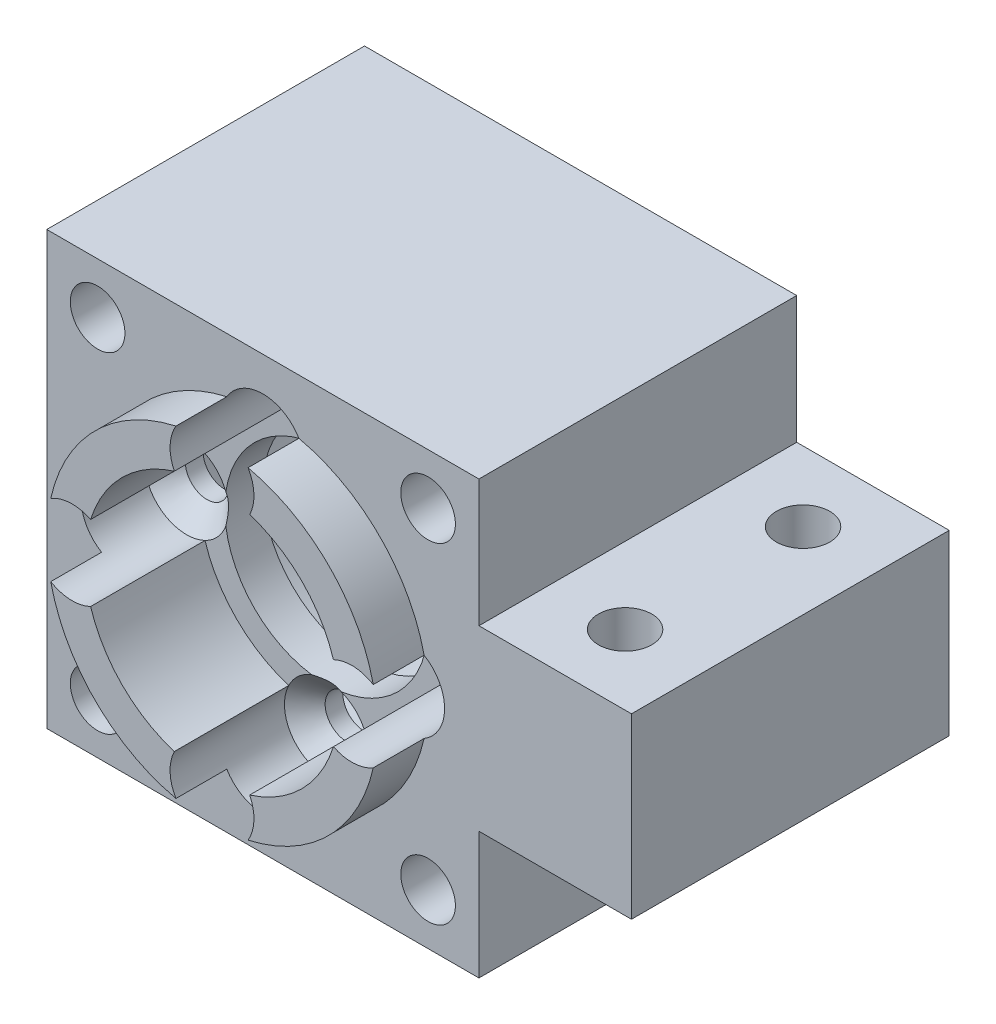
SolidWorks part; units mm, degrees
material "1060 合金"
ref_plane "前视基准面" through (0, 0, 0) normal (0, 0, 1) x (1, 0, 0)
ref_plane "上视基准面" through (0, 0, 0) normal (0, 1, 0) x (1, 0, 0)
ref_plane "右视基准面" through (0, 0, 0) normal (1, 0, 0) x (0, 0, -1)
sketch "草图1" plane through (0, 0, 0) normal (1, 0, 0) x (0, 0, -1)
  line L0 (0, 0) -> (85.2801, 0) construction
  line L1 (0, 0) -> (0, 40.8583) construction
  line L2 (0, 13) -> (0, 10)
  line L3 (0, 10) -> (9, 10)
  line L4 (9, 10) -> (9, 8)
  line L5 (9, 8) -> (12, 8)
  line L6 (12, 8) -> (12, 14)
  line L7 (12, 14) -> (29, 14)
  line L8 (29, 14) -> (29, 16)
  line L9 (29, 16) -> (4, 16)
  line L10 (0, 13) -> (4, 13)
  line L11 (4, 13) -> (4, 16)
  dimension "D1" = 8
  dimension "D2" = 3
  dimension "D3" = 13
  dimension "D4" = 14
  dimension "D5" = 2
  dimension "D6" = 17
  dimension "D7" = 4
  dimension "D8" = 8
  dimension "D9" = 10
revolve "旋转1" add sketch "草图1" angle 360 about L0
hole_wizard "打孔尺寸(%根据十字)槽沉头木螺钉的类型1" positions "草图3" profile "草图2" countersink size "M3" standard "GB" end condition through all
sketch "草图3" plane through (0, 0, 0) normal (0, 0, 1) x (1, 0, 0)
  line L0 (11, 0) -> (0, 0) construction
  line L2 (0, 0) -> (4.7674, 0) construction
  line L3 (0, 0) -> (0, 6.1766) construction
  circle A0 centre (0, 0) radius 11 construction
  point P0 (11, 0)
  point P12 (0, -11)
  point P13 (-11, 0)
  point P14 (0, 11)
  dimension "D1" = 22
  dimension "D2" = 4
sketch "草图2" plane through (11, 0, 0) normal (1, 0, 0) x (0, -1, 0)
  line L0 (0, 0) -> (0, 29)
  line L1 (0, 29) -> (1.7, 29)
  line L2 (1.7, 29) -> (1.7, 10.6)
  line L3 (1.7, 10.6) -> (3.3, 9)
  line L4 (3.3, 9) -> (3.3, 0)
  line L6 (3.3, 0) -> (0, 0)
  line L7 (-1.7, 10.6) -> (-3.3, 9) construction
  line L11 (0, -6.35) -> (0, 107.95) construction
  dimension "通孔孔直径" = 3.4
  dimension "通孔孔深度" = 29
  dimension "锥形沉头孔直径" = 6.6
  dimension "锥形沉头孔角度" = 90
  dimension "头间隙" = 9
sketch "草图4" plane through (0, 0, -4) normal (0, 0, 1) x (1, 0, 0)
  line L1 (-17, -17) -> (17, -17)
  line L2 (-17, -17) -> (-17, 17)
  line L3 (-17, 17) -> (17, 17)
  line L4 (17, -17) -> (17, 17)
  line L5 (-17, -17) -> (17, 17) construction
  line L6 (-17, 17) -> (17, -17) construction
  circle A0 centre (0, 0) radius 16
  circle A1 centre (0, 0) radius 16 construction
  point P0 (0, 0)
  dimension "D1" = 34
extrude "凸台-拉伸1" add sketch "草图4" against normal up to surface (25 mm away) up to face at (16, 0, -29)
sketch "草图11" [suppressed] plane through (0, 0, -29) normal (0, 0, -1) x (-1, 0, 0)
  line L0 (0, 0) -> (0, 25.5096) construction
  line L3 (-17, 17) -> (17, 17) construction
  line L4 (-10, 9.798) -> (10, 9.798) construction
  line L5 (-10, 9.798) -> (-10, 17)
  line L6 (-10, 17) -> (10, 17)
  line L7 (10, 9.798) -> (10, 17)
  line L8 (-10, 9.798) -> (10, 17) construction
  line L9 (-10, 17) -> (10, 9.798) construction
  circle A4 centre (0, 0) radius 14 construction
  circle A5 centre (0, 0) radius 14 construction
  arc A6 (10, 9.798) -> (-10, 9.798) centre (0, 0) ccw
  point P3 (0, 13.399)
  dimension "D1" = 20
extrude "凸台-拉伸2" [suppressed] add sketch "草图11" along normal up to surface (21 mm away)
hole_wizard "打孔尺寸(%根据)内六角圆柱头螺钉的类型2" positions "草图10" profile "草图9" counterbore size "M4" standard "GB" end condition through all
sketch "草图10" plane through (0, 0, -29) normal (0, 0, -1) x (-1, 0, 0)
  line L0 (0, 0) -> (17, 17) construction
  line L2 (17, 17) -> (17, -17) construction
  point P0 (13, 13)
  point P26 (13, -13)
  point P27 (-13, -13)
  point P28 (-13, 13)
  dimension "D1" = 4
  dimension "D2" = 4
sketch "草图9" plane through (-13, 13, -29) normal (1, 0, 0) x (0, 1, 0)
  line L0 (0, 0) -> (0, 29)
  line L1 (0, 29) -> (2.15, 29)
  line L3 (2.15, 29) -> (2.15, 11)
  line L4 (2.15, 11) -> (3.75, 11)
  line L5 (3.75, 11) -> (3.75, 0)
  line L7 (3.75, 0) -> (0, 0)
  line L11 (0, -6.35) -> (0, 107.95) construction
  dimension "通孔孔直径" = 4.3
  dimension "通孔孔深度" = 29
  dimension "柱形沉头孔直径" = 7.5
  dimension "柱形沉头孔深度" = 11
sketch "草图12" plane through (0, -17, 0) normal (0, -1, 0) x (1, 0, 0)
  line L0 (17, -4) -> (27.3244, -14.2553)
  line L1 (27.3244, -14.2553) -> (80.5693, -51.5377)
  line L2 (17, -29) -> (17, -4)
  line L3 (17, -29) -> (27.3244, -14.2553) construction
  line L4 (80.5693, -51.5377) -> (70.2449, -66.2825)
  line L5 (70.2449, -66.2825) -> (17, -29)
  dimension "D1" = 35
  dimension "D2" = 65
  dimension "D3" = 18
extrude "凸台-拉伸3" [suppressed] add sketch "草图12" against normal up to surface (34 mm away)
sketch3d "3D草图1" [suppressed]
  line L0 (0, 0, 0) -> (0, 0, 7) construction
  line L1 (0, 0, 7) -> (0, 36.7936, 7) construction
  line L2 (0, 0, 7) -> (85.6623, 0, -52.9814) construction
  line L3 (79.6572, 15.8612, -54.1479) -> (91.6674, -15.8612, -51.8149)
  line L4 (85.6623, 0, -52.9814) -> (85.6623, 15.8612, -52.9814) construction
  line L5 (85.6623, 15.8612, -52.9814) -> (82.1809, 15.8612, -50.5437) construction
  line L6 (82.1809, 15.8612, -50.5437) -> (79.6572, 15.8612, -54.1479) construction
  line L7 (82.1809, 15.8612, -50.5437) -> (85.6623, 0, -52.9814) construction
  dimension "D1" = 15
  dimension "D2" = 5
  dimension "D3" = 7
  dimension "D4" = 15
  dimension "D5" = 34
ref_axis "基准轴1" [suppressed] through (79.6572, 15.8612, -54.1479) along (0.3532, -0.933, 0.0686)
ref_point "点1" [suppressed]
sketch "草图23" [suppressed] plane through (-8.0327, 0, -11.4719) normal (-0.5736, 0, -0.8192) x (-0.8192, 0, 0.5736)
  line L0 (0, 0) -> (-89.54, 0) construction
  line L1 (4.015, 0) -> (-100.5593, 0) construction
  line L2 (-30.5593, 17) -> (-95.5593, 17) construction
  line L3 (-75.5593, -6.5) -> (-42.5593, -6.5)
  line L4 (-75.5593, -6.5) -> (-75.5593, 6.5) construction
  line L5 (-75.5593, 6.5) -> (-42.5593, 6.5)
  line L6 (-42.5593, -6.5) -> (-42.5593, 6.5) construction
  line L7 (-75.5593, -6.5) -> (-42.5593, 6.5) construction
  line L8 (-75.5593, 6.5) -> (-42.5593, -6.5) construction
  line L9 (-30.5593, 17) -> (-30.5593, -17) construction
  line L10 (-95.5593, 17) -> (-95.5593, -17) construction
  arc A0 (-75.5593, 6.5) -> (-75.5593, -6.5) centre (-75.5593, 0) ccw
  arc A1 (-42.5593, -6.5) -> (-42.5593, 6.5) centre (-42.5593, 0) ccw
  point P3 (-59.0593, 0)
  dimension "D2" = 12
  dimension "D3" = 20
  dimension "D1" = 10.5
extrude "切除-拉伸2" [suppressed] cut sketch "草图23" against normal through all
sketch "草图24" [suppressed] plane through (0, -17, 0) normal (0, -1, 0) x (1, 0, 0)
  line L0 (75.4071, -58.9101) -> (24.7393, -23.4321) construction
  line L1 (70.2449, -66.2825) -> (80.5693, -51.5377) construction
  circle A0 centre (68.8539, -54.3215) radius 4
  dimension "D1" = 8
  dimension "D2" = 8
extrude "切除-拉伸3" [suppressed] cut sketch "草图24" against normal through all
chamfer "倒角1" [suppressed] distance 6 angle 45
sketch "草图25" plane through (0, 0, 0) normal (0, 1, 0) x (1, 0, 0)
  line L1 (29, 29) -> (17, 29)
  line L2 (29, 29) -> (29, 4)
  line L3 (29, 4) -> (17, 4)
  line L4 (17, 29) -> (17, 4)
  line L5 (29, 29) -> (17, 4) construction
  line L6 (29, 4) -> (17, 29) construction
  point P0 (23, 16.5)
  dimension "D1" = 12
extrude "凸台-拉伸4" add sketch "草图25" along normal mid plane 14
hole_wizard "M5 螺纹孔1" positions "草图27" profile "草图26" tap size "M5" standard "GB" end condition up to next
sketch "草图27" plane through (0, 7, 0) normal (0, 1, 0) x (1, 0, 0)
  line L0 (29, 16.5) -> (17, 16.5) construction
  line L1 (29, 4) -> (29, 29) construction
  line L2 (17, 29) -> (17, 4) construction
  line L4 (23, 16.5) -> (23, 31.8734) construction
  point P0 (23, 23.5)
  point P2 (23, 9.5)
  dimension "D1" = 14
sketch "草图26" plane through (23, 7, -23.5) normal (1, 0, 0) x (0, 0, 1)
  line L0 (0, 0) -> (0, 14)
  line L1 (0, 14) -> (2.1, 14)
  line L2 (2.1, 14) -> (2.1, 0)
  line L5 (2.1, 0) -> (0, 0)
  line L11 (0, -6.35) -> (0, 107.95) construction
  dimension "螺纹线主直径" = 4.2
  dimension "通孔螺纹孔钻头深度" = 14
move or copy body "实体-移动/复制2" [suppressed] bodies to move or copy 138
move or copy body "实体-移动/复制1" [suppressed] bodies to move or copy 124
